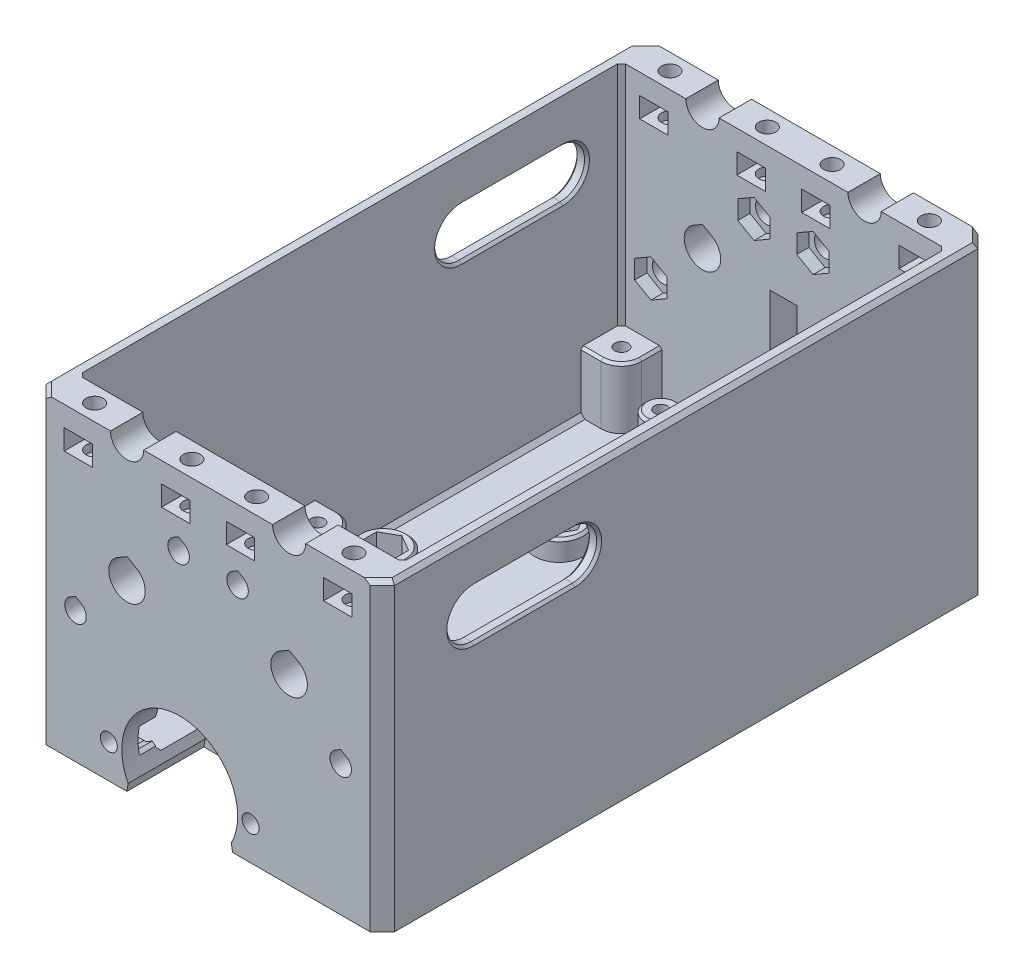
SolidWorks part; units mm, degrees
ref_plane "Front Plane" through (0, 0, 0) normal (0, 0, 1) x (1, 0, 0)
ref_plane "Top Plane" through (0, 0, 0) normal (0, 1, 0) x (1, 0, 0)
ref_plane "Right Plane" through (0, 0, 0) normal (1, 0, 0) x (0, 0, -1)
sketch "Sketch1" plane through (0, 0, 0) normal (0, 0, 1) x (1, 0, 0)
  line L0 (-15.9, 15) -> (15.9, 15)
  line L1 (20, -15) -> (-20, -15) construction
  line L2 (20, -15) -> (20, 15) construction
  line L3 (20, 15) -> (-20, 15) construction
  line L4 (-20, -15) -> (-20, 15) construction
  line L5 (20, -15) -> (-20, 15) construction
  line L6 (20, 15) -> (-20, -15) construction
  line L7 (-24.1, 15) -> (-43, 15)
  line L8 (-43, 15) -> (-43, -60)
  line L9 (-43, -60) -> (43, -60)
  line L10 (43, -60) -> (43, 15)
  line L11 (43, 15) -> (24.1, 15)
  line L12 (-24.1, 15) -> (-15.9, 15) construction
  line L13 (15.9, 15) -> (24.1, 15) construction
  line L14 (0, 0) -> (0, -60) construction
  arc A1 (-15.9, 15) -> (-24.1, 15) centre (-20, 15) cw
  arc A2 (15.9, 15) -> (24.1, 15) centre (20, 15) ccw
  circle A3 centre (-20, -15) radius 4.5
  circle A4 centre (20, -15) radius 4.5
  point P0 (0, 0)
  dimension "D3" = 9
  dimension "D1" = 40
  dimension "D2" = 30
  dimension "D4" = 8.2
  dimension "D5" = 75
  dimension "D6" = 86
extrude "Boss-Extrude1" add sketch "Sketch1" along normal mid plane 150
sketch "Sketch3" plane through (0, -60, 0) normal (0, -1, 0) x (1, 0, 0)
  line L0 (-40, 67) -> (-40, 75) construction
  line L1 (40, -67) -> (-40, -67)
  line L2 (40, -67) -> (40, 67)
  line L3 (40, 67) -> (-40, 67)
  line L4 (-40, -67) -> (-40, 67)
  line L5 (40, -67) -> (-40, 67) construction
  line L6 (40, 67) -> (-40, -67) construction
  line L7 (-43, 75) -> (43, 75) construction
  line L8 (-40, 67) -> (-43, 67) construction
  line L9 (-43, 75) -> (-43, -75) construction
  point P0 (0, 0)
  dimension "D1" = 8
  dimension "D2" = 3
extrude "Cut-Extrude1" cut sketch "Sketch3" against normal through all from offset 4 offset against normal yes
sketch "Sketch4" plane through (0, 0, 0) normal (0, 0, 1) x (1, 0, 0)
  line L0 (-32.7279, -27.7279) -> (-7.2721, -2.2721) construction
  line L1 (32.7279, -27.7279) -> (7.2721, -2.2721) construction
  line L3 (-7.2721, -2.2721) -> (7.2721, -2.2721) construction
  circle A0 centre (-7.2721, -2.2721) radius 2.65
  circle A1 centre (7.2721, -2.2721) radius 2.65
  circle A2 centre (32.7279, -27.7279) radius 2.65
  circle A3 centre (-32.7279, -27.7279) radius 2.65
  point P0 (-20, -15)
  point P1 (20, -15)
  point P8 (20, -15)
  point P11 (-20, -15)
  dimension "D3" = 5.3
  dimension "D1" = 36
  dimension "D2" = 90
extrude "Cut-Extrude2" cut sketch "Sketch4" against normal through all both and the other way through all
sketch "Sketch5" plane through (0, 15, 0) normal (0, 1, 0) x (1, 0, 0)
  line L0 (-15.9, 75) -> (-24.1, 67) construction
  line L1 (15.9, 75) -> (24.1, 67) construction
  line L2 (-15.9, -67) -> (-24.1, -75) construction
  line L3 (24.1, -67) -> (15.9, -75) construction
  line L4 (-32, -71) -> (-20, -71) construction
  line L5 (-20, -71) -> (-8, -71) construction
  line L6 (8, -71) -> (20, -71) construction
  line L7 (20, -71) -> (32, -71) construction
  line L8 (-32, 71) -> (-20, 71) construction
  line L9 (-20, 71) -> (-8, 71) construction
  line L10 (8, 71) -> (20, 71) construction
  line L11 (20, 71) -> (32, 71) construction
  circle A0 centre (-32, 71) radius 2.1
  circle A1 centre (-8, 71) radius 2.1
  circle A2 centre (8, 71) radius 2.1
  circle A3 centre (32, 71) radius 2.1
  circle A4 centre (-32, -71) radius 2.1
  circle A5 centre (-8, -71) radius 2.1
  circle A6 centre (8, -71) radius 2.1
  circle A7 centre (32, -71) radius 2.1
  dimension "D1" = 4.2
  dimension "D2" = 24
extrude "Cut-Extrude3" cut sketch "Sketch5" against normal blind 12
chamfer "Chamfer1" distance 3 angle 45 4 edges at (43, -22.5, -75) (-43, -22.5, -75) (43, -22.5, 75) (-43, -22.5, 75)
sketch "Sketch7" plane through (0, 15, 0) normal (0, 1, 0) x (1, 0, 0)
  line L1 (-35.5, 61) -> (-28.5, 61)
  line L2 (-35.5, 61) -> (-35.5, 81)
  line L3 (-35.5, 81) -> (-28.5, 81)
  line L4 (-28.5, 61) -> (-28.5, 81)
  line L5 (-35.5, 61) -> (-28.5, 81) construction
  line L6 (-35.5, 81) -> (-28.5, 61) construction
  line L7 (-11.5, 61) -> (-4.5, 61)
  line L8 (-11.5, 61) -> (-11.5, 81)
  line L9 (-11.5, 81) -> (-4.5, 81)
  line L10 (-4.5, 61) -> (-4.5, 81)
  line L11 (-11.5, 61) -> (-4.5, 81) construction
  line L12 (-11.5, 81) -> (-4.5, 61) construction
  line L13 (4.5, 61) -> (11.5, 61)
  line L14 (4.5, 61) -> (4.5, 81)
  line L15 (4.5, 81) -> (11.5, 81)
  line L16 (11.5, 61) -> (11.5, 81)
  line L17 (4.5, 61) -> (11.5, 81) construction
  line L18 (4.5, 81) -> (11.5, 61) construction
  line L19 (28.5, 61) -> (35.5, 61)
  line L20 (28.5, 61) -> (28.5, 81)
  line L21 (28.5, 81) -> (35.5, 81)
  line L22 (35.5, 61) -> (35.5, 81)
  line L23 (28.5, 61) -> (35.5, 81) construction
  line L24 (28.5, 81) -> (35.5, 61) construction
  line L25 (-35.5, -81) -> (-28.5, -81)
  line L26 (-35.5, -81) -> (-35.5, -61)
  line L27 (-35.5, -61) -> (-28.5, -61)
  line L28 (-28.5, -81) -> (-28.5, -61)
  line L29 (-35.5, -81) -> (-28.5, -61) construction
  line L30 (-35.5, -61) -> (-28.5, -81) construction
  line L31 (-11.5, -81) -> (-4.5, -81)
  line L32 (-11.5, -81) -> (-11.5, -61)
  line L33 (-11.5, -61) -> (-4.5, -61)
  line L34 (-4.5, -81) -> (-4.5, -61)
  line L35 (-11.5, -81) -> (-4.5, -61) construction
  line L36 (-11.5, -61) -> (-4.5, -81) construction
  line L37 (4.5, -81) -> (11.5, -81)
  line L38 (4.5, -81) -> (4.5, -61)
  line L39 (4.5, -61) -> (11.5, -61)
  line L40 (11.5, -81) -> (11.5, -61)
  line L41 (4.5, -81) -> (11.5, -61) construction
  line L42 (4.5, -61) -> (11.5, -81) construction
  line L43 (28.5, -81) -> (35.5, -81)
  line L44 (28.5, -81) -> (28.5, -61)
  line L45 (28.5, -61) -> (35.5, -61)
  line L46 (35.5, -81) -> (35.5, -61)
  line L47 (28.5, -81) -> (35.5, -61) construction
  line L48 (28.5, -61) -> (35.5, -81) construction
  point P0 (-32, 71)
  point P6 (-8, 71)
  point P12 (8, 71)
  point P18 (32, 71)
  point P24 (-32, -71)
  point P30 (-8, -71)
  point P36 (8, -71)
  point P42 (32, -71)
  dimension "D1" = 7
  dimension "D2" = 20
extrude "Cut-Extrude5" cut sketch "Sketch7" against normal blind 5 from offset 5 offset against normal yes
sketch "Sketch8" plane through (0, 0, 67) normal (0, 0, -1) x (-1, 0, 0)
  line L1 (-7.2721, 2.3467) -> (-11.2721, 0.0373)
  line L2 (-11.2721, 0.0373) -> (-11.2721, -4.5815)
  line L3 (-11.2721, -4.5815) -> (-7.2721, -6.8909)
  line L4 (-7.2721, -6.8909) -> (-3.2721, -4.5815)
  line L5 (-3.2721, -4.5815) -> (-3.2721, 0.0373)
  line L6 (-3.2721, 0.0373) -> (-7.2721, 2.3467)
  line L7 (7.2721, 2.3467) -> (3.2721, 0.0373)
  line L8 (3.2721, 0.0373) -> (3.2721, -4.5815)
  line L9 (3.2721, -4.5815) -> (7.2721, -6.8909)
  line L10 (7.2721, -6.8909) -> (11.2721, -4.5815)
  line L11 (11.2721, -4.5815) -> (11.2721, 0.0373)
  line L12 (11.2721, 0.0373) -> (7.2721, 2.3467)
  line L13 (-32.7279, -23.1091) -> (-36.7279, -25.4185)
  line L14 (-36.7279, -25.4185) -> (-36.7279, -30.0373)
  line L15 (-36.7279, -30.0373) -> (-32.7279, -32.3467)
  line L16 (-32.7279, -32.3467) -> (-28.7279, -30.0373)
  line L17 (-28.7279, -30.0373) -> (-28.7279, -25.4185)
  line L18 (-28.7279, -25.4185) -> (-32.7279, -23.1091)
  line L19 (32.7279, -23.1091) -> (28.7279, -25.4185)
  line L20 (28.7279, -25.4185) -> (28.7279, -30.0373)
  line L21 (28.7279, -30.0373) -> (32.7279, -32.3467)
  line L22 (32.7279, -32.3467) -> (36.7279, -30.0373)
  line L23 (36.7279, -30.0373) -> (36.7279, -25.4185)
  line L24 (36.7279, -25.4185) -> (32.7279, -23.1091)
  circle A0 centre (-7.2721, -2.2721) radius 4 construction
  circle A1 centre (7.2721, -2.2721) radius 4 construction
  circle A2 centre (-32.7279, -27.7279) radius 4 construction
  circle A3 centre (32.7279, -27.7279) radius 4 construction
  dimension "D1" = 8
extrude "Cut-Extrude6" cut sketch "Sketch8" against normal blind 3
mirror "Mirror1" about plane through (0, 0, 0) normal (0, 0, 1) of "Cut-Extrude6"
sketch "Sketch9" plane through (0, 0, 75) normal (0, 0, 1) x (1, 0, 0)
  line L0 (-22.25, -11.1029) -> (-20, -9.8038)
  line L1 (-20, -9.8038) -> (-17.75, -11.1029)
  line L2 (-17.75, -11.1029) -> (-22.25, -11.1029)
  line L3 (-8.5971, 0.0229) -> (-7.2721, 0.7879)
  line L4 (-7.2721, 0.7879) -> (-5.9471, 0.0229)
  line L5 (-5.9471, 0.0229) -> (-8.5971, 0.0229)
  line L6 (-34.0529, -25.433) -> (-32.7279, -24.668)
  line L7 (-32.7279, -24.668) -> (-31.4029, -25.433)
  line L8 (-31.4029, -25.433) -> (-34.0529, -25.433)
  line L9 (5.9471, 0.0229) -> (7.2721, 0.7879)
  line L10 (7.2721, 0.7879) -> (8.5971, 0.0229)
  line L11 (8.5971, 0.0229) -> (5.9471, 0.0229)
  line L12 (22.25, -11.1029) -> (20, -9.8038)
  line L13 (20, -9.8038) -> (17.75, -11.1029)
  line L14 (17.75, -11.1029) -> (22.25, -11.1029)
  line L15 (31.4029, -25.433) -> (32.7279, -24.668)
  line L16 (32.7279, -24.668) -> (34.0529, -25.433)
  line L17 (34.0529, -25.433) -> (31.4029, -25.433)
  line L18 (-20, -9.8038) -> (-20, -11.1029) construction
  line L19 (-32.7279, -24.668) -> (-32.7279, -25.433) construction
  line L20 (-7.2721, 0.7879) -> (-7.2721, 0.0229) construction
  line L21 (7.2721, 0.7879) -> (7.2721, 0.0229) construction
  line L22 (20, -9.8038) -> (20, -11.1029) construction
  line L23 (32.7279, -24.668) -> (32.7279, -25.433) construction
  circle A0 centre (-20, -15) radius 4.5 construction
  circle A1 centre (-7.2721, -2.2721) radius 2.65 construction
  circle A2 centre (-32.7279, -27.7279) radius 2.65 construction
  circle A3 centre (7.2721, -2.2721) radius 2.65 construction
  circle A4 centre (20, -15) radius 4.5 construction
  circle A5 centre (32.7279, -27.7279) radius 2.65 construction
  dimension "D1" = 120
  dimension "D2" = 120
  dimension "D3" = 120
  dimension "D4" = 120
  dimension "D5" = 120
  dimension "D6" = 120
extrude "Cut-Extrude7" cut sketch "Sketch9" against normal through all
sketch "Sketch11" plane through (0, -56, 0) normal (0, 1, 0) x (1, 0, 0)
  line L1 (31.7543, 0) -> (15.8771, 27.5) construction
  line L2 (15.8771, 27.5) -> (-15.8771, 27.5) construction
  line L3 (-15.8771, 27.5) -> (-31.7543, 0) construction
  line L4 (-31.7543, 0) -> (-15.8771, -27.5) construction
  line L5 (-15.8771, -27.5) -> (15.8771, -27.5) construction
  line L6 (15.8771, -27.5) -> (31.7543, 0) construction
  circle A0 centre (0, 0) radius 27.5 construction
  circle A1 centre (15.8771, 27.5) radius 2.6
  circle A2 centre (31.7543, 0) radius 2.6
  circle A3 centre (15.8771, -27.5) radius 2.6
  circle A4 centre (-15.8771, -27.5) radius 2.6
  circle A5 centre (-31.7543, 0) radius 2.6
  circle A6 centre (-15.8771, 27.5) radius 2.6
  dimension "D2" = 5.2
  dimension "D1" = 55
extrude "Cut-Extrude9" cut sketch "Sketch11" against normal through all
sketch "Sketch14" plane through (0, -56, 0) normal (0, 1, 0) x (1, 0, 0)
  line L0 (0, 0) -> (-14, 0) construction
  line L1 (-14, 0) -> (-20, 0) construction
  line L2 (0, 0) -> (14, 0) construction
  line L3 (-18.5, -4) -> (-21.5, -4) construction
  line L4 (-18.5, -4) -> (-18.5, 4) construction
  line L5 (-18.5, 4) -> (-21.5, 4) construction
  line L6 (-21.5, -4) -> (-21.5, 4) construction
  line L7 (-18.5, -4) -> (-21.5, 4) construction
  line L8 (-18.5, 4) -> (-21.5, -4) construction
  line L9 (-12.5, -4) -> (-15.5, -4) construction
  line L10 (-12.5, -4) -> (-12.5, 4) construction
  line L11 (-12.5, 4) -> (-15.5, 4) construction
  line L12 (-15.5, -4) -> (-15.5, 4) construction
  line L13 (-12.5, -4) -> (-15.5, 4) construction
  line L14 (-12.5, 4) -> (-15.5, -4) construction
  line L15 (14, 0) -> (20, 0) construction
  line L17 (15.5, -4) -> (12.5, -4)
  line L18 (15.5, -4) -> (15.5, 4)
  line L19 (15.5, 4) -> (12.5, 4)
  line L20 (12.5, -4) -> (12.5, 4)
  line L21 (15.5, -4) -> (12.5, 4) construction
  line L22 (15.5, 4) -> (12.5, -4) construction
  line L23 (21.5, -4) -> (18.5, -4)
  line L24 (21.5, -4) -> (21.5, 4)
  line L25 (21.5, 4) -> (18.5, 4)
  line L26 (18.5, -4) -> (18.5, 4)
  line L27 (21.5, -4) -> (18.5, 4) construction
  line L28 (21.5, 4) -> (18.5, -4) construction
  dimension "D1" = 8
  dimension "D2" = 3
  dimension "D3" = 6
  dimension "D4" = 14
extrude "Cut-Extrude12" cut sketch "Sketch14" against normal through all
fillet "Fillet1" radius 1 8 edges at (21.5, -58, 4) (18.5, -58, 4) (21.5, -58, -4) (18.5, -58, -4) (15.5, -58, 4) (12.5, -58, 4) (12.5, -58, -4) (15.5, -58, -4)
chamfer "Chamfer2" distance 1 angle 45 8 edges at (40, -20.5, 67) (-40, -20.5, 67) (-40, -20.5, -67) (40, -20.5, -67) (40, -56, 0) (0, -56, -67) (-40, -56, 0) (0, -56, 67)
sketch "Sketch15" plane through (0, -56, 0) normal (0, 1, 0) x (1, 0, 0)
  line L0 (-16, 18) -> (-16, 0) construction
  line L1 (-5.25, -27.5) -> (-26.75, -27.5) construction
  line L2 (-5.25, -27.5) -> (-5.25, 63.5) construction
  line L3 (-5.25, 63.5) -> (-26.75, 63.5) construction
  line L4 (-26.75, -27.5) -> (-26.75, 63.5) construction
  line L5 (-5.25, -27.5) -> (-26.75, 63.5) construction
  line L6 (-5.25, 63.5) -> (-26.75, -27.5) construction
  line L7 (-16, 0) -> (0, 0) construction
  line L8 (-8.25, -24.5) -> (-23.75, -24.5) construction
  line L9 (-8.25, -24.5) -> (-8.25, 60.5) construction
  line L10 (-8.25, 60.5) -> (-23.75, 60.5) construction
  line L11 (-23.75, -24.5) -> (-23.75, 60.5) construction
  line L12 (-8.25, -24.5) -> (-23.75, 60.5) construction
  line L13 (-8.25, 60.5) -> (-23.75, -24.5) construction
  circle A0 centre (-23.75, 60.5) radius 1.6
  circle A1 centre (-8.25, 60.5) radius 1.6
  circle A2 centre (-23.75, -24.5) radius 1.6
  circle A3 centre (-8.25, -24.5) radius 1.6
  point P0 (-16, 18)
  dimension "D6" = 3.2
  dimension "D1" = 91
  dimension "D2" = 21.5
  dimension "D3" = 18
  dimension "D4" = 15.5
  dimension "D5" = 85
  dimension "D7" = 16
extrude "Cut-Extrude13" cut sketch "Sketch15" against normal through all
sketch "Sketch16" plane through (43, 0, 0) normal (1, 0, 0) x (0, 0, -1)
  line L0 (-40, 15) -> (-40, -2) construction
  line L1 (-72, 15) -> (72, 15) construction
  line L2 (-52.5, -2) -> (-27.5, -2) construction
  line L3 (-52.5, 4) -> (-27.5, 4)
  line L4 (-52.5, -8) -> (-27.5, -8)
  arc A0 (-52.5, 4) -> (-52.5, -8) centre (-52.5, -2) ccw
  arc A1 (-27.5, -8) -> (-27.5, 4) centre (-27.5, -2) ccw
  point P6 (-40, -2)
  dimension "D1" = 12
  dimension "D2" = 17
  dimension "D3" = 25
  dimension "D4" = 40
extrude "Cut-Extrude14" cut sketch "Sketch16" against normal blind 10 and the other way through all
sketch "Sketch17" plane through (-43, 0, 0) normal (-1, 0, 0) x (0, 0, 1)
  line L0 (27.5, 4) -> (52.5, 4) construction
  line L4 (52.5, -8) -> (27.5, -8) construction
  line L5 (27.5, 4) -> (52.5, 4) construction
  line L6 (52.5, -8) -> (27.5, -8) construction
  line L7 (0, -41.25) -> (0, 41.25) construction
  line L8 (-52.5, -8) -> (-27.5, -8)
  line L9 (-27.5, 4) -> (-52.5, 4)
  arc A3 (27.5, 4) -> (27.5, -8) centre (27.5, -2) ccw construction
  arc A4 (52.5, -8) -> (52.5, 4) centre (52.5, -2) ccw construction
  arc A5 (27.5, 4) -> (27.5, -8) centre (27.5, -2) ccw construction
  arc A6 (52.5, -8) -> (52.5, 4) centre (52.5, -2) ccw construction
  arc A7 (-52.5, -8) -> (-52.5, 4) centre (-52.5, -2) cw
  arc A8 (-27.5, 4) -> (-27.5, -8) centre (-27.5, -2) cw
extrude "Cut-Extrude15" cut sketch "Sketch17" against normal blind 10
chamfer "Chamfer3" distance 1 angle 45 6 edges at (41.5, 15, -73.5) (41.5, 15, 73.5) (43, 15, 0) (-41.5, 15, -73.5) (-41.5, 15, 73.5) (-43, 15, 0)
chamfer "Chamfer4" distance 0.6 angle 45 16 edges at (43, 4, 40) (43, -2, 58.5) (43, -2, 21.5) (43, -8, 40) (40, 4, 40) (40, -2, 58.5) (40, -2, 21.5) (40, -8, 40) (-40, 4, -40) (-40, -2, -58.5) (-40, -2, -21.5) (-40, -8, -40) (-43, 4, -40) (-43, -2, -58.5) (-43, -2, -21.5) (-43, -8, -40)
sketch "Sketch18" plane through (0, -56, 0) normal (0, 1, 0) x (1, 0, 0)
  circle A0 centre (-23.75, 60.5) radius 4
  circle A1 centre (-23.75, 60.5) radius 1.6
  circle A2 centre (-8.25, 60.5) radius 4
  circle A3 centre (-8.25, 60.5) radius 1.6
  circle A4 centre (-8.25, -24.5) radius 4
  circle A5 centre (-8.25, -24.5) radius 1.6
  circle A6 centre (-23.75, -24.5) radius 4
  circle A7 centre (-23.75, -24.5) radius 1.6
  circle A8 centre (-23.75, -24.5) radius 1.6 construction
  circle A9 centre (-8.25, -24.5) radius 1.6 construction
  circle A10 centre (-23.75, 60.5) radius 1.6 construction
  circle A11 centre (-8.25, 60.5) radius 1.6 construction
  dimension "D1" = 8
extrude "Boss-Extrude2" add sketch "Sketch18" along normal blind 8
chamfer "Chamfer5" distance 0.6 angle 45 4 edges at (-23.75, -48, 28.5) (-8.25, -48, 28.5) (-23.75, -48, -56.5) (-8.25, -48, -56.5)
sketch "Sketch19" plane through (0, 0, 75) normal (0, 0, 1) x (1, 0, 0)
  line L0 (-20, -15) -> (-7, -51.637) construction
  line L1 (-7, -51.637) -> (0, -51.637) construction
  line L2 (0, -51.637) -> (0, 0) construction
  line L3 (-7, -51.637) -> (-7, -59.4312) construction
  line L4 (2.5, -66.637) -> (-16.5, -66.637)
  line L5 (2.5, -66.637) -> (2.5, -62.3253)
  line L7 (-16.5, -66.637) -> (-16.5, -62.3253)
  line L8 (2.5, -66.637) -> (-16.5, -62.3253) construction
  line L9 (2.5, -62.3253) -> (-16.5, -66.637) construction
  line L11 (-24.5, -51.637) -> (10.5, -51.637) construction
  line L12 (-7, -51.637) -> (-7, -42.037) construction
  line L13 (-7, -42.037) -> (-20, -15) construction
  arc A0 (2.5, -62.3253) -> (-16.5, -62.3253) centre (-7, -51.637) ccw
  circle A1 centre (-24.5, -51.637) radius 2.1
  circle A2 centre (10.5, -51.637) radius 2.1
  point P3 (-7, -64.4812)
  point P18 (-7, -51.637)
  dimension "D3" = 28.6
  dimension "D5" = 4.2
  dimension "D1" = 7
  dimension "D2" = 30
  dimension "D4" = 35
  dimension "D6" = 9.6
  dimension "D7" = 19
  dimension "D8" = 15
extrude "Cut-Extrude16" cut sketch "Sketch19" against normal blind 19
sketch "Sketch20" plane through (0, 0, 67) normal (0, 0, -1) x (-1, 0, 0)
  line L1 (-10.5, -47.5956) -> (-14, -49.6163)
  line L2 (-14, -49.6163) -> (-14, -53.6577)
  line L3 (-14, -53.6577) -> (-10.5, -55.6785)
  line L4 (-10.5, -55.6785) -> (-7, -53.6577)
  line L5 (-7, -53.6577) -> (-7, -49.6163)
  line L6 (-7, -49.6163) -> (-10.5, -47.5956)
  line L7 (24.5, -47.5956) -> (21, -49.6163)
  line L8 (21, -49.6163) -> (21, -53.6577)
  line L9 (21, -53.6577) -> (24.5, -55.6785)
  line L10 (24.5, -55.6785) -> (28, -53.6577)
  line L11 (28, -53.6577) -> (28, -49.6163)
  line L12 (28, -49.6163) -> (24.5, -47.5956)
  circle A0 centre (-10.5, -51.637) radius 3.5 construction
  circle A1 centre (24.5, -51.637) radius 3.5 construction
  dimension "D1" = 7
extrude "Cut-Extrude17" cut sketch "Sketch20" against normal blind 4 and the other way blind 10
chamfer "Chamfer6" distance 1 angle 45 4 edges at (-21.1444, -53.7411, 69) (-21.1444, -49.5329, 69) (7.1444, -49.5329, 69) (7.1444, -53.7411, 69) first distance on face at (-7, -52.9115, 66.2219)
sketch "Sketch21" plane through (0, -60, 0) normal (0, -1, 0) x (1, 0, 0)
  line L1 (-23.75, 27.6754) -> (-26.5, 26.0877)
  line L2 (-26.5, 26.0877) -> (-26.5, 22.9123)
  line L3 (-26.5, 22.9123) -> (-23.75, 21.3246)
  line L4 (-23.75, 21.3246) -> (-21, 22.9123)
  line L5 (-21, 22.9123) -> (-21, 26.0877)
  line L6 (-21, 26.0877) -> (-23.75, 27.6754)
  line L7 (-8.25, 27.6754) -> (-11, 26.0877)
  line L8 (-11, 26.0877) -> (-11, 22.9123)
  line L9 (-11, 22.9123) -> (-8.25, 21.3246)
  line L10 (-8.25, 21.3246) -> (-5.5, 22.9123)
  line L11 (-5.5, 22.9123) -> (-5.5, 26.0877)
  line L12 (-5.5, 26.0877) -> (-8.25, 27.6754)
  line L13 (-8.25, -57.3246) -> (-11, -58.9123)
  line L14 (-11, -58.9123) -> (-11, -62.0877)
  line L15 (-11, -62.0877) -> (-8.25, -63.6754)
  line L16 (-8.25, -63.6754) -> (-5.5, -62.0877)
  line L17 (-5.5, -62.0877) -> (-5.5, -58.9123)
  line L18 (-5.5, -58.9123) -> (-8.25, -57.3246)
  line L19 (-23.75, -57.3246) -> (-26.5, -58.9123)
  line L20 (-26.5, -58.9123) -> (-26.5, -62.0877)
  line L21 (-26.5, -62.0877) -> (-23.75, -63.6754)
  line L22 (-23.75, -63.6754) -> (-21, -62.0877)
  line L23 (-21, -62.0877) -> (-21, -58.9123)
  line L24 (-21, -58.9123) -> (-23.75, -57.3246)
  circle A0 centre (-23.75, 24.5) radius 2.75 construction
  circle A1 centre (-8.25, 24.5) radius 2.75 construction
  circle A2 centre (-8.25, -60.5) radius 2.75 construction
  circle A3 centre (-23.75, -60.5) radius 2.75 construction
  dimension "D1" = 5.5
extrude "Cut-Extrude18" cut sketch "Sketch21" against normal blind 3.2
sketch "Sketch22" plane through (0, -56, 0) normal (0, 1, 0) x (1, 0, 0)
  line L1 (-13.5966, -23.55) -> (-18.1577, -23.55)
  line L2 (-18.1577, -23.55) -> (-20.4382, -27.5)
  line L3 (-20.4382, -27.5) -> (-18.1577, -31.45)
  line L4 (-18.1577, -31.45) -> (-13.5966, -31.45)
  line L5 (-13.5966, -31.45) -> (-11.3161, -27.5)
  line L6 (-11.3161, -27.5) -> (-13.5966, -23.55)
  line L7 (-27.8043, 2.2805) -> (-31.7543, 4.5611)
  line L8 (-31.7543, 4.5611) -> (-35.7043, 2.2805)
  line L9 (-35.7043, 2.2805) -> (-35.7043, -2.2805)
  line L10 (-35.7043, -2.2805) -> (-31.7543, -4.5611)
  line L11 (-31.7543, -4.5611) -> (-27.8043, -2.2805)
  line L12 (-27.8043, -2.2805) -> (-27.8043, 2.2805)
  line L13 (31.7543, 4.5611) -> (27.8043, 2.2805)
  line L14 (27.8043, 2.2805) -> (27.8043, -2.2805)
  line L15 (27.8043, -2.2805) -> (31.7543, -4.5611)
  line L16 (31.7543, -4.5611) -> (35.7043, -2.2805)
  line L17 (35.7043, -2.2805) -> (35.7043, 2.2805)
  line L18 (35.7043, 2.2805) -> (31.7543, 4.5611)
  line L19 (18.1577, 31.45) -> (13.5966, 31.45)
  line L20 (13.5966, 31.45) -> (11.3161, 27.5)
  line L21 (11.3161, 27.5) -> (13.5966, 23.55)
  line L22 (13.5966, 23.55) -> (18.1577, 23.55)
  line L23 (18.1577, 23.55) -> (20.4382, 27.5)
  line L24 (20.4382, 27.5) -> (18.1577, 31.45)
  line L25 (-13.5966, 31.45) -> (-18.1577, 31.45)
  line L26 (-18.1577, 31.45) -> (-20.4382, 27.5)
  line L27 (-20.4382, 27.5) -> (-18.1577, 23.55)
  line L28 (-18.1577, 23.55) -> (-13.5966, 23.55)
  line L29 (-13.5966, 23.55) -> (-11.3161, 27.5)
  line L30 (-11.3161, 27.5) -> (-13.5966, 31.45)
  line L31 (18.1577, -23.55) -> (13.5966, -23.55)
  line L32 (13.5966, -23.55) -> (11.3161, -27.5)
  line L33 (11.3161, -27.5) -> (13.5966, -31.45)
  line L34 (13.5966, -31.45) -> (18.1577, -31.45)
  line L35 (18.1577, -31.45) -> (20.4382, -27.5)
  line L36 (20.4382, -27.5) -> (18.1577, -23.55)
  circle A0 centre (-15.8771, -27.5) radius 3.95 construction
  circle A1 centre (-31.7543, 0) radius 3.95 construction
  circle A2 centre (31.7543, 0) radius 3.95 construction
  circle A3 centre (15.8771, 27.5) radius 3.95 construction
  circle A4 centre (-15.8771, 27.5) radius 3.95 construction
  circle A5 centre (15.8771, -27.5) radius 3.95 construction
  circle A6 centre (-15.8771, 27.5) radius 6
  circle A7 centre (15.8771, 27.5) radius 6
  circle A8 centre (-31.7543, 0) radius 6
  circle A9 centre (31.7543, 0) radius 6
  circle A10 centre (15.8771, -27.5) radius 6
  circle A11 centre (-15.8771, -27.5) radius 6
  dimension "D2" = 12
  dimension "D1" = 7.9
extrude "Boss-Extrude3" add sketch "Sketch22" along normal blind 5
chamfer "Chamfer7" distance 0.6 angle 45 7 edges at (31.7543, -51, 6) (-15.9997, -51, 21.5013) (-15.9356, -51, 33.4997) (-31.7543, -51, 6) (15.8771, -51, -21.5) (-15.8771, -51, -21.5) (15.8771, -51, 33.5)
chamfer "Chamfer8" distance 2 angle 45 2 edges at (-18.5996, -60, 65.5) (4.5996, -60, 65.5) first distance on face at (-7, -52.9679, 66.2219)
sketch "Sketch24" plane through (-40, 0, 0) normal (1, 0, 0) x (0, 0, -1)
  line L0 (0, 0) -> (0, -43) construction
  line L1 (0, -43) -> (-50, -43) construction
  line L2 (-66, 15) -> (66, 15) construction
  line L3 (-47.1039, -50.35) -> (-52.8961, -50.35)
  line L4 (-47.1039, -50.35) -> (-47.1039, -35.65) construction
  line L5 (-47.1039, -35.65) -> (-52.8961, -35.65)
  line L6 (-52.8961, -50.35) -> (-52.8961, -35.65) construction
  line L7 (-47.1039, -50.35) -> (-52.8961, -35.65) construction
  line L8 (-47.1039, -35.65) -> (-52.8961, -50.35) construction
  arc A0 (-52.8961, -35.65) -> (-52.8961, -50.35) centre (-50, -43) ccw
  arc A1 (-47.1039, -50.35) -> (-47.1039, -35.65) centre (-50, -43) ccw
  dimension "D1" = 15.8
  dimension "D2" = 14.7
  dimension "D3" = 58
  dimension "D4" = 50
extrude "Cut-Extrude19" cut sketch "Sketch24" against normal through all
sketch "Sketch25" plane through (0, 0, -75) normal (0, 0, -1) x (-1, 0, 0)
  line L0 (0, 0) -> (0, -30) construction
  line L2 (-3.3, -40.5) -> (3.3, -40.5)
  line L3 (-3.3, -40.5) -> (-3.3, -19.5)
  line L4 (-3.3, -19.5) -> (3.3, -19.5)
  line L5 (3.3, -40.5) -> (3.3, -19.5)
  line L6 (-3.3, -40.5) -> (3.3, -19.5) construction
  line L7 (-3.3, -19.5) -> (3.3, -40.5) construction
  dimension "D1" = 6.6
  dimension "D2" = 21
  dimension "D3" = 30
extrude "Cut-Extrude20" cut sketch "Sketch25" against normal blind 10
sketch "Sketch26" plane through (-3.3, 0, 0) normal (1, 0, 0) x (0, 0, -1)
  line L0 (67, -40.5) -> (75, -40.5) construction
  line L1 (80, -40.5) -> (75, -40.5)
  line L2 (80, -40.5) -> (80, -19.5)
  line L3 (80, -19.5) -> (75, -19.5)
  line L4 (75, -40.5) -> (75, -19.5)
  line L5 (80, -40.5) -> (75, -19.5) construction
  line L6 (80, -19.5) -> (75, -40.5) construction
  line L7 (77.5, -25.25) -> (77.5, -34.75) construction
  circle A0 centre (77.5, -25.25) radius 1.15
  circle A1 centre (77.5, -34.75) radius 1.15
  point P0 (77.5, -30)
  point P10 (77.5, -30)
  point P13 (84.0571, -19.8)
  dimension "D1" = 2.3
  dimension "D2" = 9.5
  dimension "D3" = 5
extrude "Boss-Extrude4" add sketch "Sketch26" against normal blind 3
chamfer "Chamfer9" distance 4 angle 45 1 edges at (0, -19.5, -67)
sketch "Sketch27" plane through (0, -56, 0) normal (0, 1, 0) x (1, 0, 0)
  line L0 (18, 50) -> (18, 0) construction
  line L1 (33.5, 37.5) -> (2.5, 37.5) construction
  line L2 (33.5, 37.5) -> (33.5, 62.5) construction
  line L3 (33.5, 62.5) -> (2.5, 62.5) construction
  line L4 (2.5, 37.5) -> (2.5, 62.5) construction
  line L5 (33.5, 37.5) -> (2.5, 62.5) construction
  line L6 (33.5, 62.5) -> (2.5, 37.5) construction
  line L7 (18, 0) -> (0, 0) construction
  circle A0 centre (2.5, 62.5) radius 1.6
  circle A1 centre (33.5, 62.5) radius 1.6
  circle A2 centre (33.5, 37.5) radius 1.6
  circle A3 centre (2.5, 37.5) radius 1.6
  point P0 (18, 50)
  dimension "D1" = 3.2
  dimension "D2" = 31
  dimension "D3" = 25
  dimension "D4" = 18
  dimension "D5" = 50
extrude "Cut-Extrude21" cut sketch "Sketch27" against normal through all
sketch "Sketch28" plane through (0, -56, 0) normal (0, 1, 0) x (1, 0, 0)
  circle A0 centre (2.5, 37.5) radius 3.1
  circle A1 centre (2.5, 37.5) radius 1.6
  circle A2 centre (2.5, 62.5) radius 3.1
  circle A3 centre (2.5, 62.5) radius 1.6
  circle A4 centre (33.5, 62.5) radius 3.1
  circle A5 centre (33.5, 62.5) radius 1.6
  circle A6 centre (33.5, 37.5) radius 3.1
  circle A7 centre (33.5, 37.5) radius 1.6
  circle A8 centre (2.5, 37.5) radius 1.6 construction
  dimension "D1" = 6.2
extrude "Boss-Extrude5" add sketch "Sketch28" along normal blind 5
chamfer "Chamfer10" distance 1.2 angle 45 4 edges at (33.5, -56, -65.6) (33.5, -56, -40.6) (2.5, -56, -40.6) (2.5, -56, -65.6)
chamfer "Chamfer11" distance 0.6 angle 45 4 edges at (2.5, -51, -34.4) (33.5, -51, -34.4) (33.5, -51, -59.4) (2.5, -51, -59.4)
chamfer "Chamfer12" distance 1.2 angle 45 4 edges at (-4.5276, -56, 23.0359) (-27.4878, -56, 23.0757) (-8.25, -56, -64.5) (-23.75, -56, -64.5)
sketch "Sketch29" plane through (0, -56.8, 0) normal (0, -1, 0) x (1, 0, 0)
  line L0 (-5.5, -62.0877) -> (-5.5, -58.9123) construction
  line L1 (2.5, -34.3246) -> (-0.25, -35.9123)
  line L2 (-0.25, -35.9123) -> (-0.25, -39.0877)
  line L3 (-0.25, -39.0877) -> (2.5, -40.6754)
  line L4 (2.5, -40.6754) -> (5.25, -39.0877)
  line L5 (5.25, -39.0877) -> (5.25, -35.9123)
  line L6 (5.25, -35.9123) -> (2.5, -34.3246)
  line L7 (33.5, -34.3246) -> (30.75, -35.9123)
  line L8 (30.75, -35.9123) -> (30.75, -39.0877)
  line L9 (30.75, -39.0877) -> (33.5, -40.6754)
  line L10 (33.5, -40.6754) -> (36.25, -39.0877)
  line L11 (36.25, -39.0877) -> (36.25, -35.9123)
  line L12 (36.25, -35.9123) -> (33.5, -34.3246)
  line L13 (33.5, -59.3246) -> (30.75, -60.9123)
  line L14 (30.75, -60.9123) -> (30.75, -64.0877)
  line L15 (30.75, -64.0877) -> (33.5, -65.6754)
  line L16 (33.5, -65.6754) -> (36.25, -64.0877)
  line L17 (36.25, -64.0877) -> (36.25, -60.9123)
  line L18 (36.25, -60.9123) -> (33.5, -59.3246)
  line L19 (2.5, -59.3246) -> (-0.25, -60.9123)
  line L20 (-0.25, -60.9123) -> (-0.25, -64.0877)
  line L21 (-0.25, -64.0877) -> (2.5, -65.6754)
  line L22 (2.5, -65.6754) -> (5.25, -64.0877)
  line L23 (5.25, -64.0877) -> (5.25, -60.9123)
  line L24 (5.25, -60.9123) -> (2.5, -59.3246)
  circle A0 centre (2.5, -37.5) radius 2.75 construction
  circle A1 centre (33.5, -37.5) radius 2.75 construction
  circle A2 centre (33.5, -62.5) radius 2.75 construction
  circle A3 centre (2.5, -62.5) radius 2.75 construction
extrude "Cut-Extrude22" cut sketch "Sketch29" along normal through all
sketch "Sketch30" plane through (-3.3, 0, 0) normal (1, 0, 0) x (0, 0, -1)
  line L0 (80, -40.5) -> (75, -45.5)
  line L1 (75, -45.5) -> (75, -40.5)
  line L2 (67, -40.5) -> (75, -40.5) construction
  line L3 (75, -40.5) -> (80, -40.5)
  point P3 (75.7116, -44.7884)
extrude "Boss-Extrude6" add sketch "Sketch30" against normal up to surface (3 mm away) up to face at (-6.3, -33.6, -77.5)
chamfer "Chamfer13" distance 1.2 angle 45 1 edges at (-4.8, -19.5, -80)
sketch "Sketch31" plane through (0, 0, 0) normal (0, 1, 0) x (1, 0, 0)
  line L0 (0, 0) -> (35, 0) construction
  line L1 (35, 0) -> (35, -22) construction
  line L2 (35, -22) -> (35, -62) construction
  line L3 (35, 0) -> (35, 22) construction
  line L4 (0, 0) -> (0, -36) construction
  line L5 (0, 0) -> (-35, 0) construction
  line L6 (-35, 0) -> (-35, -13) construction
  line L7 (-35, 0) -> (-35, 62) construction
  circle A0 centre (-35, -13) radius 1.65
  circle A1 centre (-35, 62) radius 1.65
  circle A2 centre (0, -36) radius 1.65
  circle A3 centre (35, -62) radius 1.65
  circle A4 centre (35, -22) radius 1.65
  circle A5 centre (35, 22) radius 1.65
  dimension "D9" = 3.3
  dimension "D1" = 35
  dimension "D2" = 35
  dimension "D3" = 22
  dimension "D4" = 22
  dimension "D5" = 62
  dimension "D6" = 13
  dimension "D7" = 62
  dimension "D8" = 36
extrude "Cut-Extrude23" cut sketch "Sketch31" against normal through all
sketch "Sketch32" plane through (0, -56, 0) normal (0, 1, 0) x (1, 0, 0)
  line L0 (-30, 62) -> (-30, 67)
  line L1 (-30, 67) -> (-40, 67)
  line L2 (-40, 67) -> (-40, 57)
  line L3 (-40, 57) -> (-35, 57)
  line L4 (-35, -8) -> (-40, -8)
  line L5 (-40, -8) -> (-40, -18)
  line L6 (-40, -18) -> (-35, -18)
  line L7 (35, -17) -> (40, -17)
  line L8 (40, -17) -> (40, -27)
  line L9 (40, -27) -> (35, -27)
  line L10 (35, 27) -> (40, 27)
  line L11 (40, 27) -> (40, 17)
  line L12 (40, 17) -> (35, 17)
  line L13 (-40, -66) -> (-40, 66) construction
  line L14 (-39, 67) -> (39, 67) construction
  line L15 (40, 66) -> (40, -66) construction
  line L16 (30, -62) -> (30, -67)
  line L17 (30, -67) -> (40, -67)
  line L18 (40, -67) -> (40, -57)
  line L19 (40, -57) -> (35, -57)
  line L20 (39, -67) -> (11.6751, -67) construction
  arc A0 (-30, 62) -> (-35, 57) centre (-35, 62) cw
  arc A1 (35, 27) -> (35, 17) centre (35, 22) ccw
  arc A2 (35, -17) -> (35, -27) centre (35, -22) ccw
  arc A3 (-35, -8) -> (-35, -18) centre (-35, -13) cw
  circle A4 centre (0, -36) radius 5
  arc A5 (35, -57) -> (30, -62) centre (35, -62) ccw
  circle A6 centre (-35, -13) radius 1.65
  circle A7 centre (0, -36) radius 1.65
  circle A8 centre (35, -22) radius 1.65
  circle A9 centre (35, -62) radius 1.65
  circle A10 centre (35, 22) radius 1.65
  circle A11 centre (-35, 62) radius 1.65
  circle A12 centre (-35, -13) radius 1.65 construction
  circle A13 centre (0, -36) radius 1.65 construction
  point P54 (-33.3763, -16.8352)
  point P55 (-40, -9.3374)
  point P56 (35.3337, 17.9222)
  point P57 (34.6727, -25.9933)
  dimension "D1" = 10
  dimension "D2" = 10
extrude "Boss-Extrude7" add sketch "Sketch32" along normal blind 15
sketch "Sketch33" plane through (0, -41, 0) normal (0, 1, 0) x (1, 0, 0)
  line L1 (-33.4123, 64.75) -> (-36.5877, 64.75)
  line L2 (-36.5877, 64.75) -> (-38.1754, 62)
  line L3 (-38.1754, 62) -> (-36.5877, 59.25)
  line L4 (-36.5877, 59.25) -> (-33.4123, 59.25)
  line L5 (-33.4123, 59.25) -> (-31.8246, 62)
  line L6 (-31.8246, 62) -> (-33.4123, 64.75)
  line L7 (36.5877, 24.75) -> (33.4123, 24.75)
  line L8 (33.4123, 24.75) -> (31.8246, 22)
  line L9 (31.8246, 22) -> (33.4123, 19.25)
  line L10 (33.4123, 19.25) -> (36.5877, 19.25)
  line L11 (36.5877, 19.25) -> (38.1754, 22)
  line L12 (38.1754, 22) -> (36.5877, 24.75)
  line L13 (36.5877, -19.25) -> (33.4123, -19.25)
  line L14 (33.4123, -19.25) -> (31.8246, -22)
  line L15 (31.8246, -22) -> (33.4123, -24.75)
  line L16 (33.4123, -24.75) -> (36.5877, -24.75)
  line L17 (36.5877, -24.75) -> (38.1754, -22)
  line L18 (38.1754, -22) -> (36.5877, -19.25)
  line L19 (36.5877, -59.25) -> (33.4123, -59.25)
  line L20 (33.4123, -59.25) -> (31.8246, -62)
  line L21 (31.8246, -62) -> (33.4123, -64.75)
  line L22 (33.4123, -64.75) -> (36.5877, -64.75)
  line L23 (36.5877, -64.75) -> (38.1754, -62)
  line L24 (38.1754, -62) -> (36.5877, -59.25)
  line L25 (-1.5877, -33.25) -> (-3.1754, -36)
  line L26 (-3.1754, -36) -> (-1.5877, -38.75)
  line L27 (-1.5877, -38.75) -> (1.5877, -38.75)
  line L28 (1.5877, -38.75) -> (3.1754, -36)
  line L29 (3.1754, -36) -> (1.5877, -33.25)
  line L30 (1.5877, -33.25) -> (-1.5877, -33.25)
  line L31 (-33.4123, -10.25) -> (-36.5877, -10.25)
  line L32 (-36.5877, -10.25) -> (-38.1754, -13)
  line L33 (-38.1754, -13) -> (-36.5877, -15.75)
  line L34 (-36.5877, -15.75) -> (-33.4123, -15.75)
  line L35 (-33.4123, -15.75) -> (-31.8246, -13)
  line L36 (-31.8246, -13) -> (-33.4123, -10.25)
  circle A0 centre (-35, 62) radius 2.75 construction
  circle A1 centre (35, 22) radius 2.75 construction
  circle A2 centre (35, -22) radius 2.75 construction
  circle A3 centre (35, -62) radius 2.75 construction
  circle A4 centre (0, -36) radius 2.75 construction
  circle A5 centre (-35, -13) radius 2.75 construction
  point P46 (36.4068, 24.6351)
  dimension "D1" = 5.5
extrude "Cut-Extrude24" cut sketch "Sketch33" against normal through all from offset 6 offset against normal yes
chamfer "Chamfer14" distance 0.6 angle 45 16 edges at (37.5, -41, 57) (30, -41, 64.5) (31.4645, -41, 58.4645) (37.5, -41, 17) (37.5, -41, 27) (30, -41, 22) (37.5, -41, -27) (37.5, -41, -17) (30, -41, -22) (0, -41, 41) (-37.5, -41, 18) (-37.5, -41, 8) (-30, -41, 13) (-37.5, -41, -57) (-31.4645, -41, -58.4645) (-30, -41, -64.5)
sketch "Sketch34" plane through (0, 0, -67) normal (0, 0, 1) x (1, 0, 0)
  line L0 (0, 0) -> (0, -50) construction
  line L4 (0, -50) -> (-16, -50) construction
  circle A0 centre (-16, -50) radius 3
  dimension "D3" = 6
  dimension "D1" = 16
  dimension "D2" = 50
extrude "Cut-Extrude26" cut sketch "Sketch34" against normal blind 15
sketch "Sketch35" plane through (0, 0, -75) normal (0, 0, -1) x (-1, 0, 0)
  line L0 (0, 0) -> (0, -50) construction
  line L1 (0, -50) -> (-4, -50) construction
  line L2 (0, -50) -> (4, -50) construction
  line L4 (-6, -53) -> (-2, -53)
  line L5 (-6, -53) -> (-6, -47)
  line L6 (-6, -47) -> (-2, -47)
  line L7 (-2, -53) -> (-2, -47)
  line L8 (-6, -53) -> (-2, -47) construction
  line L9 (-6, -47) -> (-2, -53) construction
  line L10 (2, -53) -> (6, -53)
  line L11 (2, -53) -> (2, -47)
  line L12 (2, -47) -> (6, -47)
  line L13 (6, -53) -> (6, -47)
  line L14 (2, -53) -> (6, -47) construction
  line L15 (2, -47) -> (6, -53) construction
  dimension "D1" = 4
  dimension "D2" = 6
  dimension "D3" = 50
  dimension "D4" = 8
extrude "Cut-Extrude27" cut sketch "Sketch35" against normal blind 9
sketch "Sketch36" plane through (0, -56, 0) normal (0, 1, 0) x (1, 0, 0)
  line L0 (-11, -49) -> (-3, -49) construction
  line L1 (-7, -49) -> (-7, -56) construction
  line L2 (6.6182, -56) -> (-20.6182, -56) construction
  line L4 (-9.5, -52.5) -> (-12.5, -52.5)
  line L5 (-9.5, -52.5) -> (-9.5, -45.5)
  line L6 (-9.5, -45.5) -> (-12.5, -45.5)
  line L7 (-12.5, -52.5) -> (-12.5, -45.5)
  line L8 (-9.5, -52.5) -> (-12.5, -45.5) construction
  line L9 (-9.5, -45.5) -> (-12.5, -52.5) construction
  line L10 (-1.5, -52.5) -> (-4.5, -52.5)
  line L11 (-1.5, -52.5) -> (-1.5, -45.5)
  line L12 (-1.5, -45.5) -> (-4.5, -45.5)
  line L13 (-4.5, -52.5) -> (-4.5, -45.5)
  line L14 (-1.5, -52.5) -> (-4.5, -45.5) construction
  line L15 (-1.5, -45.5) -> (-4.5, -52.5) construction
  dimension "D1" = 3
  dimension "D2" = 7
  dimension "D3" = 8
  dimension "D4" = 7
extrude "Cut-Extrude28" cut sketch "Sketch36" against normal through all
fillet "Fillet2" radius 1 8 edges at (-1.5, -58, 45.5) (-4.5, -58, 45.5) (-1.5, -58, 52.5) (-4.5, -58, 52.5) (-9.5, -58, 52.5) (-12.5, -58, 52.5) (-9.5, -58, 45.5) (-12.5, -58, 45.5)
chamfer "Chamfer15" distance 2 angle 45 1 edges at (-7, -56, 56)
